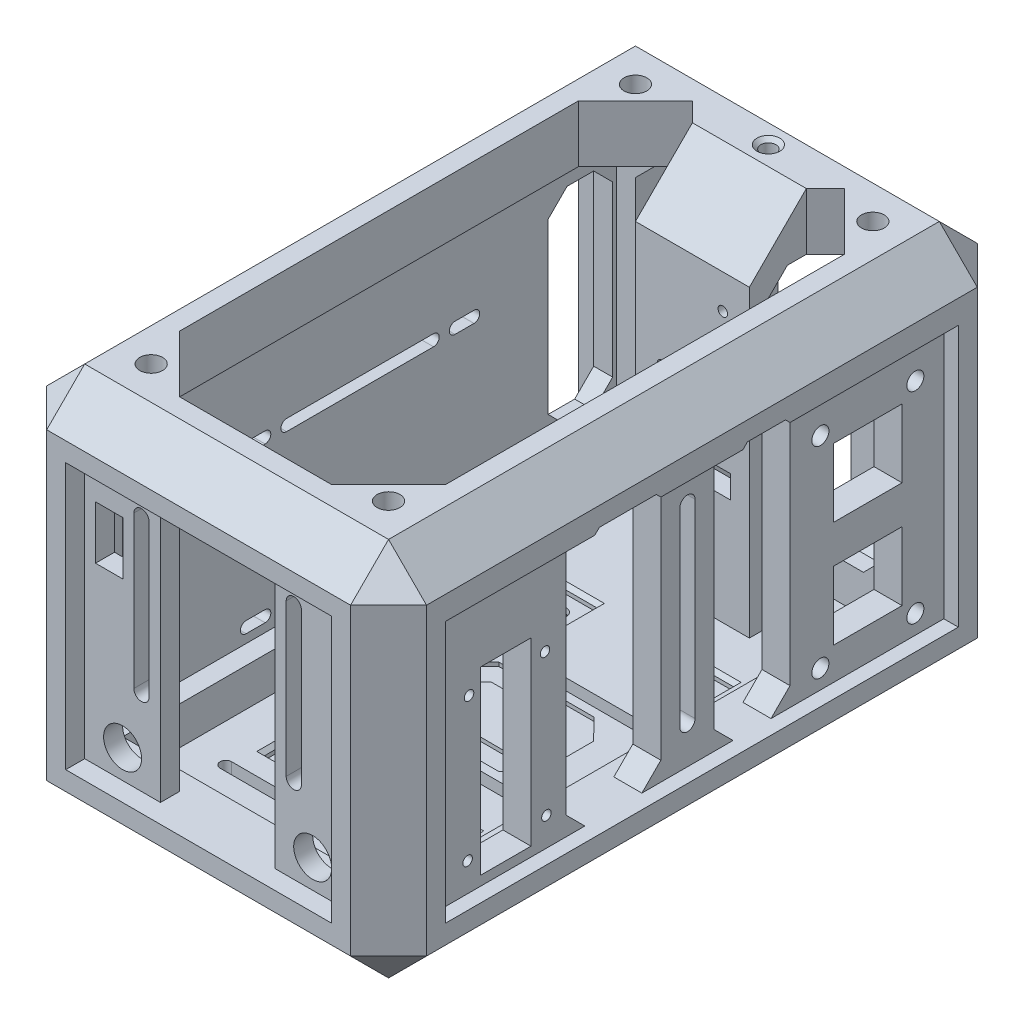
SolidWorks part; units mm, degrees
ref_plane "Front Plane" through (0, 0, 0) normal (0, 0, 1) x (1, 0, 0)
ref_plane "Top Plane" through (0, 0, 0) normal (0, 1, 0) x (1, 0, 0)
ref_plane "Right Plane" through (0, 0, 0) normal (1, 0, 0) x (0, 0, -1)
sketch "Sketch1" plane through (0, 0, 0) normal (0, 0, 1) x (1, 0, 0)
  line L1 (0, 0) -> (100, 0)
  line L2 (0, 0) -> (0, 100)
  line L3 (0, 100) -> (100, 100)
  line L4 (100, 0) -> (100, 100)
  dimension "D1" = 100
  dimension "D2" = 100
extrude "Main Cube" add sketch "Sketch1" against normal blind 165
chamfer "Main Cube Chamfer" distance 10 angle 45 12 edges at (50, 0, -165) (100, 50, -165) (0, 50, -165) (0, 0, -82.5) (0, 50, 0) (50, 0, 0) (100, 0, -82.5) (100, 50, 0) (50, 100, -165) (0, 100, -82.5) (50, 100, 0) (100, 100, -82.5)
sketch "Sketch2" plane through (0, 0, 0) normal (-1, 0, 0) x (0, 0, 1)
  line L1 (-155, 90) -> (-10, 90)
  line L2 (-155, 90) -> (-155, 10)
  line L3 (-155, 10) -> (-10, 10)
  line L4 (-10, 90) -> (-10, 10)
  line L5 (-150, 85) -> (-15, 85)
  line L6 (-150, 85) -> (-150, 15)
  line L7 (-150, 15) -> (-15, 15)
  line L8 (-15, 85) -> (-15, 15)
  dimension "D1" = 5
  dimension "D2" = 5
  dimension "D3" = 5
  dimension "D4" = 5
extrude "Main Cube Hollow Out 1" cut sketch "Sketch2" against normal up to surface (100 mm away) contours L8 L5 L6 L7 region at (0, 50, -82.5) up to face at (100, 50, -82.5)
sketch "Sketch3" plane through (0, 0, -165) normal (0, 0, -1) x (-1, 0, 0)
  line L1 (-90, 90) -> (-10, 90)
  line L2 (-90, 90) -> (-90, 10)
  line L3 (-90, 10) -> (-10, 10)
  line L4 (-10, 90) -> (-10, 10)
  line L5 (-85, 85) -> (-15, 85)
  line L6 (-85, 85) -> (-85, 15)
  line L7 (-85, 15) -> (-15, 15)
  line L8 (-15, 85) -> (-15, 15)
  dimension "D1" = 5
  dimension "D2" = 5
  dimension "D3" = 5
  dimension "D4" = 5
extrude "Main Cube Hollow Out 2" cut sketch "Sketch3" against normal up to surface (165 mm away) contours L8 L5 L6 L7 region at (50, 50, -165) up to face at (50, 50, 0)
sketch "Sketch4" plane through (0, 100, 0) normal (0, 1, 0) x (1, 0, 0)
  line L1 (90, 155) -> (10, 155)
  line L2 (90, 155) -> (90, 10)
  line L3 (90, 10) -> (10, 10)
  line L4 (10, 155) -> (10, 10)
  line L5 (85, 150) -> (15, 150)
  line L6 (85, 150) -> (85, 15)
  line L7 (85, 15) -> (15, 15)
  line L8 (15, 150) -> (15, 15)
  dimension "D1" = 5
  dimension "D2" = 5
  dimension "D3" = 5
  dimension "D4" = 5
extrude "Main Cube Hollow Out 3" cut sketch "Sketch4" against normal up to surface (100 mm away) contours L5 L8 L7 L6 region at (50, 100, -82.5) up to face at (50, 0, -82.5)
sketch "Sketch5" plane through (0, 0, 0) normal (0, -1, 0) x (1, 0, 0)
  line L1 (15, -15) -> (85, -15)
  line L2 (15, -15) -> (15, -150)
  line L3 (15, -150) -> (85, -150)
  line L4 (85, -15) -> (85, -150)
extrude "Bottom" add sketch "Sketch5" against normal blind 5
sketch "Sketch6" plane through (0, 15, 0) normal (0, 1, 0) x (1, 0, 0)
  line L0 (15, 0) -> (15, 15) construction
  line L1 (15, 10) -> (85, 10)
  line L2 (15, 10) -> (15, 5)
  line L3 (15, 5) -> (85, 5)
  line L4 (85, 10) -> (85, 5)
  line L5 (85, 0) -> (85, 15) construction
  line L6 (15, 10) -> (15, 15) construction
  line L7 (15, 5) -> (15, 0) construction
  dimension "D1" = 5
extrude "Camera and Temp Sensor Wall" add sketch "Sketch6" along normal up to surface (70 mm away) up to face at (92.5, 85, -82.5)
sketch "Sketch7" plane through (0, 0, -5) normal (0, 0, 1) x (1, 0, 0)
  line L0 (50, 85) -> (50, 15) construction
  line L1 (85, 85) -> (15, 85) construction
  line L2 (15, 15) -> (85, 15) construction
  line L3 (15, 50) -> (85, 50) construction
  line L4 (15, 85) -> (15, 15) construction
  line L5 (85, 15) -> (85, 85) construction
  line L6 (50, 30) -> (50, 85) construction
  line L8 (34.95, 30) -> (34.95, 85)
  line L9 (34.95, 85) -> (65.05, 85)
  line L10 (65.05, 30) -> (65.05, 85)
  line L11 (15, 22.5) -> (85, 22.5) construction
  line L12 (58.2839, 30) -> (58.2839, 22.5) construction
  line L13 (58.2839, 22.5) -> (58.2839, 15) construction
  line L14 (34.95, 30) -> (24.975, 30) construction
  line L15 (24.975, 30) -> (24.975, 22.5) construction
  line L16 (24.975, 30) -> (15, 30) construction
  line L17 (15, 15) -> (15, 85) construction
  line L18 (65.05, 30) -> (75.025, 30) construction
  line L19 (75.025, 30) -> (75.025, 22.5) construction
  line L20 (75.025, 30) -> (85, 30) construction
  line L21 (85, 85) -> (85, 15) construction
  line L22 (29.95, 77.5) -> (29.95, 37.5) construction
  line L23 (31.95, 77.5) -> (31.95, 37.5)
  line L24 (27.95, 77.5) -> (27.95, 37.5)
  line L25 (70.05, 77.5) -> (70.05, 37.5) construction
  line L26 (72.05, 77.5) -> (72.05, 37.5)
  line L27 (68.05, 77.5) -> (68.05, 37.5)
  line L28 (15, 85) -> (85, 85) construction
  line L29 (15, 15) -> (85, 15) construction
  line L31 (34.95, 30) -> (34.95, 15)
  line L32 (34.95, 15) -> (65.05, 15)
  line L33 (65.05, 30) -> (65.05, 15)
  line L34 (17.85, 69.7469) -> (15, 69.7469) construction
  line L35 (17.85, 75) -> (25.1, 75)
  line L36 (17.85, 75) -> (17.85, 61)
  line L37 (17.85, 61) -> (25.1, 61)
  line L38 (25.1, 75) -> (25.1, 61)
  line L39 (25.1, 69.7469) -> (27.95, 69.7469) construction
  line L40 (34.95, 82.5532) -> (15, 82.5532) construction
  line L41 (65.05, 81.9311) -> (85, 81.9311) construction
  line L42 (31.95, 48.3508) -> (34.95, 48.3508) construction
  line L43 (65.05, 48.3508) -> (68.05, 48.3508) construction
  line L44 (21.475, 75) -> (21.475, 85) construction
  circle A0 centre (24.975, 22.5) radius 5
  circle A1 centre (75.025, 22.5) radius 5
  arc A2 (31.95, 77.5) -> (27.95, 77.5) centre (29.95, 77.5) ccw
  arc A3 (27.95, 37.5) -> (31.95, 37.5) centre (29.95, 37.5) ccw
  arc A4 (72.05, 77.5) -> (68.05, 77.5) centre (70.05, 77.5) ccw
  arc A5 (68.05, 37.5) -> (72.05, 37.5) centre (70.05, 37.5) ccw
  point P36 (29.95, 57.5)
  point P41 (70.05, 57.5)
  dimension "D3" = 10
  dimension "D4" = 10
  dimension "D1" = 30.1
  dimension "D2" = 55
  dimension "D5" = 7.5
  dimension "D6" = 7.25
  dimension "D7" = 7.5
  dimension "D8" = 7.5
  dimension "D9" = 5
  dimension "D10" = 5
  dimension "D11" = 4
  dimension "D12" = 4
  dimension "D13" = 14
  dimension "D14" = 30.1
  dimension "D15" = 10
extrude "Camera and Ext. Temp Sensor Through Holes" cut sketch "Sketch7" against normal up to surface (5 mm away) up to face at (50, 50, -10)
sketch "Sketch8" plane through (0, 15, 0) normal (0, 1, 0) x (1, 0, 0)
  line L0 (15, 150) -> (0, 150) construction
  line L1 (10, 150) -> (5, 150)
  line L2 (10, 150) -> (10, 15)
  line L3 (10, 15) -> (5, 15)
  line L4 (5, 150) -> (5, 15)
  line L5 (15, 15) -> (0, 15) construction
  line L6 (15, 15) -> (10, 15) construction
  line L7 (5, 15) -> (0, 15) construction
  dimension "D1" = 5
extrude "Antenna and Battery Bracket" add sketch "Sketch8" along normal up to surface (70 mm away) up to face at (92.5, 85, -82.5)
chamfer "Top Chamfer 1" distance 5 angle 45 6 edges at (75.025, 85, -10) (24.975, 85, -10) (75.025, 85, -5) (24.975, 85, -5) (65.05, 85, -7.5) (34.95, 85, -7.5)
sketch "Sketch9" plane through (5, 0, 0) normal (-1, 0, 0) x (0, 0, 1)
  line L0 (-136.9322, 71.5) -> (-28.0678, 71.5) construction
  line L1 (-136.9322, 80) -> (-28.0678, 80)
  line L2 (-136.9322, 63) -> (-28.0678, 63)
  line L3 (-82.5, 71.5) -> (-82.5, 85) construction
  line L4 (-150, 85) -> (-15, 85) construction
  line L5 (-112.5, 82.5) -> (-107.5, 82.5) construction
  line L6 (-112.5, 84) -> (-107.5, 84)
  line L7 (-112.5, 81) -> (-107.5, 81)
  line L8 (-52.5, 82.5) -> (-57.5, 82.5) construction
  line L9 (-52.5, 81) -> (-57.5, 81)
  line L10 (-52.5, 84) -> (-57.5, 84)
  line L11 (-52.5, 59.5) -> (-57.5, 59.5) construction
  line L12 (-52.5, 58) -> (-57.5, 58)
  line L13 (-52.5, 61) -> (-57.5, 61)
  line L14 (-107.5, 59.5) -> (-112.5, 59.5) construction
  line L15 (-107.5, 58) -> (-112.5, 58)
  line L16 (-107.5, 61) -> (-112.5, 61)
  line L17 (-110, 84) -> (-110, 85) construction
  line L18 (-15, 85) -> (-150, 85) construction
  line L19 (-110, 81) -> (-110, 80) construction
  line L20 (-110, 61) -> (-110, 63) construction
  line L21 (-55, 61) -> (-55, 63) construction
  line L22 (-55, 81) -> (-55, 80) construction
  line L23 (-55, 84) -> (-55, 85) construction
  line L24 (-110, 84.5) -> (-150, 84.5) construction
  line L25 (-150, 85) -> (-150, 15) construction
  line L26 (-110, 62.5) -> (-150, 62.5) construction
  line L27 (-150, 85) -> (-150, 15) construction
  line L28 (-55, 62.5) -> (-15, 62.5) construction
  line L29 (-55, 84.5) -> (-15, 84.5) construction
  line L30 (-15, 85) -> (-15, 15) construction
  line L31 (-150, 85) -> (-150, 15) construction
  line L32 (-150, 39.25) -> (-15, 39.25) construction
  line L33 (-132.3966, 39.25) -> (-132.3966, 63) construction
  line L34 (-132.3966, 39.25) -> (-132.3966, 15) construction
  line L35 (-150, 15) -> (-15, 15) construction
  line L36 (-101.8419, 59.5) -> (-63.1581, 59.5) construction
  line L37 (-34, 22.5) -> (-131, 22.5)
  line L38 (-34, 22.5) -> (-34, 56)
  line L39 (-34, 56) -> (-131, 56)
  line L40 (-131, 22.5) -> (-131, 56)
  line L41 (-34, 22.5) -> (-131, 56) construction
  line L42 (-34, 56) -> (-131, 22.5) construction
  line L43 (-101.8419, 61) -> (-63.1581, 61)
  line L44 (-101.8419, 58) -> (-63.1581, 58)
  line L45 (-101.8419, 59.5) -> (-107.5, 59.5) construction
  line L46 (-63.1581, 59.5) -> (-57.5, 59.5) construction
  line L47 (-55, 58) -> (-55, 56) construction
  line L48 (-110, 58) -> (-110, 56) construction
  line L49 (-101.8419, 18.75) -> (-63.1581, 18.75) construction
  line L50 (-101.8419, 20.25) -> (-63.1581, 20.25)
  line L51 (-101.8419, 17.25) -> (-63.1581, 17.25)
  line L52 (-57.5, 18.75) -> (-52.5, 18.75) construction
  line L53 (-57.5, 20.25) -> (-52.5, 20.25)
  line L54 (-57.5, 17.25) -> (-52.5, 17.25)
  line L55 (-107.5, 18.75) -> (-112.5, 18.75) construction
  line L56 (-107.5, 17.25) -> (-112.5, 17.25)
  line L57 (-107.5, 20.25) -> (-112.5, 20.25)
  line L58 (-82.5, 18.75) -> (-82.5, 22.5) construction
  line L59 (-82.5, 18.75) -> (-82.5, 15) construction
  line L60 (-63.1581, 82.5) -> (-101.8419, 82.5) construction
  line L61 (-63.1581, 81) -> (-101.8419, 81)
  line L62 (-63.1581, 84) -> (-101.8419, 84)
  line L63 (-150, 47.1044) -> (-149, 47.1044) construction
  line L64 (-149, 77) -> (-132, 77)
  line L65 (-149, 77) -> (-149, 22.5)
  line L66 (-149, 22.5) -> (-132, 22.5)
  line L67 (-132, 77) -> (-132, 22.5)
  line L68 (-33, 22.5) -> (-16, 22.5)
  line L69 (-33, 22.5) -> (-33, 77)
  line L70 (-33, 77) -> (-16, 77)
  line L71 (-16, 22.5) -> (-16, 77)
  line L72 (-132, 47.1044) -> (-131, 47.1044) construction
  line L73 (-34, 47.1044) -> (-33, 47.1044) construction
  line L74 (-16, 47.1044) -> (-15, 47.1044) construction
  line L75 (-146.1678, 77) -> (-146.1678, 84.5) construction
  line L76 (-146.1678, 22.5) -> (-146.1678, 15) construction
  line L77 (-150, 15) -> (-15, 15) construction
  arc A0 (-136.9322, 80) -> (-136.9322, 63) centre (-136.9322, 71.5) ccw
  arc A1 (-28.0678, 63) -> (-28.0678, 80) centre (-28.0678, 71.5) ccw
  arc A2 (-112.5, 84) -> (-112.5, 81) centre (-112.5, 82.5) ccw
  arc A3 (-107.5, 81) -> (-107.5, 84) centre (-107.5, 82.5) ccw
  arc A4 (-52.5, 81) -> (-52.5, 84) centre (-52.5, 82.5) ccw
  arc A5 (-57.5, 84) -> (-57.5, 81) centre (-57.5, 82.5) ccw
  arc A6 (-52.5, 58) -> (-52.5, 61) centre (-52.5, 59.5) ccw
  arc A7 (-57.5, 61) -> (-57.5, 58) centre (-57.5, 59.5) ccw
  arc A8 (-107.5, 58) -> (-107.5, 61) centre (-107.5, 59.5) ccw
  arc A9 (-112.5, 61) -> (-112.5, 58) centre (-112.5, 59.5) ccw
  arc A10 (-101.8419, 61) -> (-101.8419, 58) centre (-101.8419, 59.5) ccw
  arc A11 (-63.1581, 58) -> (-63.1581, 61) centre (-63.1581, 59.5) ccw
  arc A12 (-101.8419, 20.25) -> (-101.8419, 17.25) centre (-101.8419, 18.75) ccw
  arc A13 (-63.1581, 17.25) -> (-63.1581, 20.25) centre (-63.1581, 18.75) ccw
  arc A14 (-57.5, 20.25) -> (-57.5, 17.25) centre (-57.5, 18.75) ccw
  arc A15 (-52.5, 17.25) -> (-52.5, 20.25) centre (-52.5, 18.75) ccw
  arc A16 (-107.5, 17.25) -> (-107.5, 20.25) centre (-107.5, 18.75) ccw
  arc A17 (-112.5, 20.25) -> (-112.5, 17.25) centre (-112.5, 18.75) ccw
  arc A18 (-63.1581, 81) -> (-63.1581, 84) centre (-63.1581, 82.5) ccw
  arc A19 (-101.8419, 84) -> (-101.8419, 81) centre (-101.8419, 82.5) ccw
  point P2 (-82.5, 71.5)
  point P13 (-110, 82.5)
  point P18 (-55, 82.5)
  point P25 (-55, 59.5)
  point P32 (-110, 59.5)
  point P77 (-82.5, 39.25)
  point P87 (-82.5, 59.5)
  point P102 (-82.5, 18.75)
  point P107 (-55, 18.75)
  point P114 (-110, 18.75)
  point P126 (-82.5, 82.5)
  dimension "D2" = 5
  dimension "D3" = 5
  dimension "D4" = 5
  dimension "D5" = 5
  dimension "D6" = 3
  dimension "D7" = 3
  dimension "D8" = 3
  dimension "D9" = 3
  dimension "D10" = 40
  dimension "D11" = 40
  dimension "D12" = 97
  dimension "D13" = 33.5
  dimension "D14" = 1
  dimension "D15" = 2
  dimension "D16" = 17
  dimension "D17" = 3
  dimension "D18" = 5
  dimension "D19" = 5
  dimension "D20" = 1
  dimension "D21" = 1
extrude "Antenna and Battery Zip Tie Holes" cut sketch "Sketch9" against normal up to surface (5 mm away) contours L68 L71 L70 L69 | L67 L64 L65 L66 | L64 A0 L2 L67 | L2 A1 L70 L69 | L6 A3 L7 A2 | L10 A5 L9 A4 | L13 A7 L12 A6 | L43 A11 L44 A10 | L16 A9 L15 A8 | L57 A17 L56 A16 | L50 A13 L51 A12 | L53 A15 L54 A14 | L62 A19 L61 A18 region at (5, 45.1526, -141.0251) region at (5, 70.3505, -138.1472) region at (5, 70.3505, -26.8528) region at (5, 45.1526, -23.9749) up to face at (10, 50, -82.5)
chamfer "Antenna And Battery Wire Pass throughs" distance 5 angle 45 8 edges at (7.5, 22.5, -33) (7.5, 22.5, -16) (7.5, 77, -16) (7.5, 77, -33) (7.5, 77, -149) (7.5, 77, -132) (7.5, 22.5, -132) (7.5, 22.5, -149)
chamfer "Top Chamfer 2" distance 5 angle 45 2 edges at (5, 85, -82.5) (10, 85, -82.5)
sketch "Sketch10" plane through (0, 15, 0) normal (0, 1, 0) x (1, 0, 0)
  line L0 (100, 15) -> (85, 15) construction
  line L1 (88.8093, 15) -> (96.1907, 15)
  line L2 (88.8093, 15) -> (88.8093, 150)
  line L3 (88.8093, 150) -> (96.1907, 150)
  line L4 (96.1907, 15) -> (96.1907, 150)
  line L5 (100, 150) -> (85, 150) construction
  line L6 (88.8093, 15) -> (85, 15) construction
  line L7 (96.1907, 15) -> (100, 15) construction
extrude "SD Card Board and Perf Board Wall" add sketch "Sketch10" along normal up to surface (70 mm away) contours L2 L1 L4 L3 up to face at (92.5, 85, -82.5)
sketch "Sketch11" plane through (96.1907, 0, 0) normal (1, 0, 0) x (0, 0, -1)
  line L0 (25, 60) -> (45, 60) construction
  line L1 (24.625, 22.5) -> (45.375, 22.5) construction
  line L2 (35, 60) -> (35, 22.5) construction
  line L4 (15, 15) -> (150, 15) construction
  line L5 (35, 20) -> (15, 20) construction
  line L6 (15, 85) -> (15, 15) construction
  line L8 (28, 65) -> (41.3059, 65)
  line L9 (28, 65) -> (28, 17.5)
  line L10 (28, 17.5) -> (41.3059, 17.5)
  line L11 (41.3059, 65) -> (41.3059, 17.5)
  line L12 (150, 85) -> (15, 85) construction
  line L14 (25, 60) -> (35, 60) construction
  line L15 (35, 60) -> (45, 60) construction
  line L16 (130, 85) -> (130, 15) construction
  line L17 (117.5, 73) -> (142.5, 73) construction
  line L18 (117.5, 20) -> (142.5, 20) construction
  line L19 (117.5, 20) -> (117.5, 45) construction
  line L20 (139, 51.5) -> (121, 51.5)
  line L21 (139, 51.5) -> (139, 69.5)
  line L22 (139, 69.5) -> (121, 69.5)
  line L23 (121, 51.5) -> (121, 69.5)
  line L24 (139, 51.5) -> (121, 69.5) construction
  line L25 (139, 69.5) -> (121, 51.5) construction
  line L26 (139, 23.5) -> (121, 23.5)
  line L27 (139, 23.5) -> (139, 41.5)
  line L28 (139, 41.5) -> (121, 41.5)
  line L29 (121, 23.5) -> (121, 41.5)
  line L30 (139, 23.5) -> (121, 41.5) construction
  line L31 (139, 41.5) -> (121, 23.5) construction
  line L32 (117.5, 45) -> (142.5, 45) construction
  line L33 (142.5, 45) -> (142.5, 20) construction
  line L34 (121, 39.018) -> (117.5, 39.018) construction
  line L35 (124.5972, 41.5) -> (124.5972, 45) construction
  line L36 (139, 39.018) -> (142.5, 39.018) construction
  line L37 (124.5972, 23.5) -> (124.5972, 20) construction
  line L38 (117.5, 73) -> (117.5, 48) construction
  line L39 (117.5, 48) -> (142.5, 48) construction
  line L40 (142.5, 48) -> (142.5, 73) construction
  line L41 (124.5972, 51.5) -> (124.5972, 48) construction
  line L42 (124.5972, 69.5) -> (124.5972, 73) construction
  line L43 (117.5, 71.1246) -> (121, 71.1246) construction
  line L44 (139, 71.1246) -> (142.5, 71.1246) construction
  line L45 (150, 85) -> (150, 15) construction
  line L46 (82.5, 85) -> (82.5, 15) construction
  line L47 (150, 15) -> (15, 15) construction
  line L48 (82.5, 75) -> (82.5, 25) construction
  line L49 (84.5, 75) -> (84.5, 25)
  line L50 (80.5, 75) -> (80.5, 25)
  line L51 (150, 85) -> (15, 85) construction
  line L52 (75.5, 15) -> (50.5, 15)
  line L53 (75.5, 15) -> (75.5, 85)
  line L54 (75.5, 85) -> (50.5, 85)
  line L55 (50.5, 15) -> (50.5, 85)
  line L57 (89.5, 85) -> (109.5, 85)
  line L58 (89.5, 85) -> (89.5, 15)
  line L59 (89.5, 15) -> (109.5, 15)
  line L60 (109.5, 85) -> (109.5, 15)
  circle A0 centre (25, 60) radius 1.25
  circle A1 centre (24.625, 22.5) radius 1.25
  circle A2 centre (45.375, 22.5) radius 1.25
  circle A3 centre (45, 60) radius 1.25
  circle A4 centre (117.5, 73) radius 2.25
  circle A5 centre (142.5, 73) radius 2.25
  circle A6 centre (142.5, 20) radius 2.25
  circle A7 centre (117.5, 20) radius 2.25
  arc A8 (84.5, 75) -> (80.5, 75) centre (82.5, 75) ccw
  arc A9 (80.5, 25) -> (84.5, 25) centre (82.5, 25) ccw
  point P37 (130, 20)
  point P38 (130, 50)
  point P39 (130, 60.5)
  point P44 (130, 32.5)
  point P49 (130, 73)
  point P78 (82.5, 50)
  dimension "D3" = 2.5
  dimension "D4" = 2.5
  dimension "D5" = 2.5
  dimension "D6" = 2.5
  dimension "D12" = 4.5
  dimension "D13" = 4.5
  dimension "D14" = 4.5
  dimension "D15" = 4.5
  dimension "D1" = 20.75
  dimension "D2" = 20
  dimension "D7" = 37.5
  dimension "D8" = 5
  dimension "D9" = 20
  dimension "D10" = 5
  dimension "D11" = 3
  dimension "D16" = 25
  dimension "D17" = 25
  dimension "D18" = 18
  dimension "D19" = 18
  dimension "D20" = 5
  dimension "D21" = 25
  dimension "D22" = 25
  dimension "D23" = 10
  dimension "D24" = 7.5
  dimension "D25" = 10
  dimension "D26" = 10
  dimension "D27" = 4
  dimension "D28" = 5
  dimension "D29" = 5
  dimension "D30" = 25
  dimension "D31" = 20
  dimension "D32" = 7.5
extrude "SD Card Board and Perf Board Through Holes" cut sketch "Sketch11" against normal up to surface (7.3814 mm away) up to face at (88.8093, 50, -82.5)
chamfer "Top Chamfer 3" distance 5 angle 45 14 edges at (92.5, 15, -75.5) (92.5, 15, -50.5) (96.1907, 85, -129.75) (92.5, 85, -109.5) (92.5, 85, -89.5) (96.1907, 85, -82.5) (92.5, 85, -75.5) (92.5, 85, -50.5) (96.1907, 85, -32.75) (88.8093, 85, -129.75) (88.8093, 85, -82.5) (88.8093, 85, -32.75) (92.5, 15, -89.5) (92.5, 15, -109.5)
sketch "Sketch13" plane through (0, 5, 0) normal (0, 1, 0) x (1, 0, 0)
  line L0 (15, 150) -> (85, 150) construction
  line L1 (35, 150) -> (65, 150)
  line L2 (35, 150) -> (35, 130)
  line L3 (35, 130) -> (65, 130)
  line L4 (65, 150) -> (65, 130)
  line L5 (15, 150) -> (35, 150) construction
  line L6 (65, 150) -> (85, 150) construction
  dimension "D1" = 30
  dimension "D2" = 20
extrude "Pressure Sensor Bracket 1" add sketch "Sketch13" along normal up to surface (10 mm away) up to face at (50, 15, -7.5)
sketch "Sketch14" plane through (0, 15, 0) normal (0, 1, 0) x (1, 0, 0)
  line L0 (65, 130) -> (65, 150) construction
  line L1 (35, 130) -> (65, 130)
  line L2 (35, 130) -> (35, 135)
  line L3 (35, 135) -> (65, 135)
  line L4 (65, 130) -> (65, 135)
  dimension "D1" = 5
extrude "Pressure Sensor Bracket 2" add sketch "Sketch14" along normal up to surface (85 mm away) up to face at (50, 100, -82.5)
sketch "Sketch16" plane through (0, 100, 0) normal (0, 1, 0) x (1, 0, 0)
  line L1 (35, 135) -> (65, 135)
  line L2 (35, 135) -> (35, 150)
  line L3 (35, 150) -> (65, 150)
  line L4 (65, 135) -> (65, 150)
extrude "Pressure Sensor Bracket 3" add sketch "Sketch16" against normal up to surface (15 mm away) up to face at (92.5, 85, -99.5)
sketch "Sketch17" plane through (0, 15, 0) normal (0, 1, 0) x (1, 0, 0)
  line L0 (65, 135) -> (35, 135) construction
  line L1 (65, 150) -> (60, 150)
  line L2 (65, 150) -> (65, 135)
  line L3 (65, 135) -> (60, 135)
  line L4 (60, 150) -> (60, 135)
  line L6 (35, 150) -> (40, 150)
  line L7 (35, 150) -> (35, 135)
  line L8 (35, 135) -> (40, 135)
  line L9 (40, 150) -> (40, 135)
  dimension "D1" = 5
  dimension "D2" = 5
extrude "Pressure Sensor Bracket 4" add sketch "Sketch17" along normal blind 20
chamfer "Top Chamfer 4" distance 5 angle 45 1 edges at (50, 85, -135)
chamfer "Pressure Sensor Bracket Chamfer" distance 5 angle 45 4 edges at (37.5, 35, -150) (62.5, 35, -150) (37.5, 35, -135) (62.5, 35, -135)
chamfer "Top Chamfer 5" distance 10 angle 45 2 edges at (85, 85, -157.5) (15, 85, -157.5)
chamfer "Bottom Chamfer 1" distance 10 angle 45 2 edges at (15, 15, -157.5) (85, 15, -157.5)
sketch "Sketch18" plane through (35, 0, 0) normal (-1, 0, 0) x (0, 0, 1)
  line L0 (-150, 22.5) -> (-130, 22.5) construction
  line L1 (-150, 30) -> (-150, 15) construction
  line L2 (-130, 100) -> (-130, 5) construction
  circle A0 centre (-140, 22.5) radius 5
  dimension "D1" = 10
extrude "Wire Management Hole" cut sketch "Sketch18" against normal up to surface (30 mm away) up to face at (65, 51.25, -142.0833)
sketch "Sketch19" plane through (0, 0, -135) normal (0, 0, -1) x (-1, 0, 0)
  line L0 (-60, 40) -> (-40, 40) construction
  line L1 (-50, 40) -> (-50, 48) construction
  line L2 (-50, 48) -> (-56.35, 48) construction
  line L3 (-50, 48) -> (-43.65, 48) construction
  line L4 (-60, 40) -> (-60, 22.5) construction
  line L5 (-60, 34) -> (-40, 34)
  line L6 (-60, 34) -> (-60, 40)
  line L7 (-60, 40) -> (-40, 40)
  line L8 (-40, 34) -> (-40, 40)
  line L10 (-40, 40) -> (-35, 40) construction
  circle A0 centre (-56.35, 48) radius 1.25
  circle A1 centre (-43.65, 48) radius 1.25
  dimension "D1" = 2.5
  dimension "D2" = 2.5
  dimension "D3" = 12.7
  dimension "D4" = 6
  dimension "D5" = 8
extrude "Pressure Sensor Through Hole" cut sketch "Sketch19" against normal up to surface (5 mm away) up to face at (50, 52.5, -130)
sketch "Sketch20" plane through (0, 15, 0) normal (0, 1, 0) x (1, 0, 0)
  line L0 (75, 165) -> (25, 165) construction
  line L1 (70, 165) -> (62.5, 165)
  line L2 (70, 165) -> (70, 159.3045)
  line L3 (70, 159.3045) -> (62.5, 159.3045)
  line L4 (62.5, 165) -> (62.5, 159.3045)
  line L5 (75, 165) -> (70, 165) construction
  line L6 (30, 165) -> (37.5, 165)
  line L7 (30, 165) -> (30, 159.3045)
  line L8 (30, 159.3045) -> (37.5, 159.3045)
  line L9 (37.5, 165) -> (37.5, 159.3045)
  line L10 (30, 165) -> (25, 165) construction
  dimension "D1" = 5
  dimension "D2" = 7.5
extrude "Boss-Extrude13" add sketch "Sketch20" along normal up to surface (70 mm away) up to face at (92.5, 85, -99.5)
sketch "Sketch21" plane through (0, 0, -165) normal (0, 0, -1) x (-1, 0, 0)
  line L0 (-15, 25) -> (-30, 25)
  line L1 (-30, 85) -> (-30, 15) construction
  line L2 (-30, 25) -> (-30, 15)
  line L3 (-30, 15) -> (-25, 15)
  line L4 (-25, 15) -> (-15, 25)
  line L5 (-85, 25) -> (-70, 25)
  line L6 (-70, 85) -> (-70, 15) construction
  line L7 (-70, 25) -> (-70, 15)
  line L8 (-70, 15) -> (-75.025, 15)
  line L9 (-85, 15) -> (-65.05, 15) construction
  line L10 (-75.025, 15) -> (-85, 25)
extrude "Boss-Extrude14" add sketch "Sketch21" against normal up to surface (5.6955 mm away) up to face at (66.25, 50, -159.3045)
chamfer "Chamfer10" distance 5 angle 45 2 edges at (31.25, 15, -159.3045) (68.75, 15, -159.3045)
chamfer "Chamfer11" distance 5 angle 45 2 edges at (37.5, 15, -159.6523) (62.5, 15, -159.6523)
chamfer "Chamfer12" distance 5 angle 45 2 edges at (37.5, 85, -162.1523) (62.5, 85, -162.1523)
chamfer "Chamfer14" distance 15 angle 45 1 edges at (50, 100, -130)
sketch "Sketch23" plane through (0, 15, 0) normal (0, 1, 0) x (1, 0, 0)
  line L0 (50, 135) -> (50, 165) construction
  line L1 (60, 135) -> (40, 135) construction
  line L2 (57.5, 165) -> (42.5, 165) construction
  line L3 (60, 150) -> (40, 150) construction
  circle A0 centre (50, 150) radius 2
  dimension "D1" = 4
extrude "Cut-Extrude9" cut sketch "Sketch23" against normal up to surface and the other way up to surface up to face at (50, 0, -82.5) other way up to face at (50, 100, -115)
chamfer "Chamfer15" distance 1 angle 45 3 edges at (50, 0, -152) (50, 15, -152) (50, 100, -148)
sketch "Sketch24" plane through (0, 5, 0) normal (0, 1, 0) x (1, 0, 0)
  line L0 (50, 130) -> (50, 15) construction
  line L1 (35, 130) -> (65, 130) construction
  line L2 (85, 15) -> (15, 15) construction
  line L3 (72.5, 117.3146) -> (27.5, 117.3146) construction
  line L4 (72.5, 117.3146) -> (72.5, 40.8146) construction
  line L5 (72.5, 40.8146) -> (27.5, 40.8146) construction
  line L6 (27.5, 40.8146) -> (27.5, 117.3146) construction
  line L7 (63, 117.3146) -> (63, 117.8146)
  line L8 (72.5, 117.3146) -> (63, 117.3146)
  line L9 (72.5, 117.3146) -> (72.5, 107.8146)
  line L10 (72.5, 107.8146) -> (63, 107.8146)
  line L11 (63, 117.3146) -> (63, 107.8146)
  line L12 (27.5, 117.3146) -> (37, 117.3146)
  line L13 (27.5, 117.3146) -> (27.5, 107.8146)
  line L14 (27.5, 107.8146) -> (37, 107.8146)
  line L15 (37, 117.3146) -> (37, 107.8146)
  line L16 (27.5, 40.8146) -> (37, 40.8146)
  line L17 (27.5, 40.8146) -> (27.5, 50.3146)
  line L18 (27.5, 50.3146) -> (37, 50.3146)
  line L19 (37, 40.8146) -> (37, 50.3146)
  line L20 (72.5, 40.8146) -> (63, 40.8146)
  line L21 (72.5, 40.8146) -> (72.5, 50.0646)
  line L22 (72.5, 50.0646) -> (63, 50.0646)
  line L23 (63, 40.8146) -> (63, 50.0646)
  line L24 (63, 117.8146) -> (73, 117.8146)
  line L25 (73, 117.8146) -> (73, 107.8146)
  line L26 (73, 107.8146) -> (72.5, 107.8146)
  line L27 (72.5, 50.0646) -> (73, 50.0646)
  line L28 (73, 50.0646) -> (73, 40.3146)
  line L29 (73, 40.3146) -> (63, 40.3146)
  line L30 (63, 40.3146) -> (63, 40.8146)
  line L31 (37, 40.8146) -> (37, 40.3146)
  line L32 (37, 40.3146) -> (27, 40.3146)
  line L33 (27, 40.3146) -> (27, 50.3146)
  line L34 (27, 50.3146) -> (27.5, 50.3146)
  line L35 (37, 117.3146) -> (37, 117.8146)
  line L36 (37, 117.8146) -> (27, 117.8146)
  line L37 (27, 117.8146) -> (27, 107.8146)
  line L38 (27, 107.8146) -> (27.5, 107.8146)
  point P6 (50, 117.3146)
  dimension "D1" = 76.5
  dimension "D2" = 45
  dimension "D3" = 9.5
  dimension "D4" = 9.5
  dimension "D5" = 9.5
  dimension "D6" = 9.5
  dimension "D7" = 9.5
  dimension "D8" = 9.5
  dimension "D9" = 9.25
  dimension "D10" = 9.5
  dimension "D11" = 0.5
  dimension "D12" = 0.5
  dimension "D13" = 0.5
  dimension "D14" = 0.5
  dimension "D15" = 0.5
  dimension "D16" = 0.5
  dimension "D17" = 0.5
  dimension "D18" = 0.5
extrude "Cut-Extrude10" cut sketch "Sketch24" against normal blind 2 contours L26 L25 L24 L7 L8 L9 | L8 L11 L10 L9 | L37 L38 L13 L12 L35 L36 | L15 L12 L13 L14 | L34 L33 L32 L31 L16 L17 | L16 L19 L18 L17 | L23 L20 L21 L22 | L30 L29 L28 L27 L21 L20 region at (63.1414, 5, -117.5646) region at (67.75, 5, -112.5646) region at (27.3586, 5, -112.5646) region at (32.25, 5, -112.5646) region at (32.25, 5, -45.5646) region at (32.25, 5, -40.6732) region at (72.6397, 5, -45.4396) region at (67.75, 5, -45.4396)
chamfer "Chamfer16" distance 1 angle 45 16 edges at (68, 5, -40.3146) (73, 5, -45.1896) (68, 5, -50.0646) (63, 5, -45.1896) (27, 5, -45.3146) (32, 5, -40.3146) (37, 5, -45.3146) (32, 5, -50.3146) (27, 5, -112.8146) (32, 5, -107.8146) (32, 5, -117.8146) (37, 5, -112.8146) (63, 5, -112.8146) (68, 5, -107.8146) (73, 5, -112.8146) (68, 5, -117.8146)
sketch "Sketch25" plane through (0, 3, 0) normal (0, 1, 0) x (1, 0, 0)
  line L0 (73, 117.8146) -> (63, 107.8146) construction
  line L1 (63, 117.8146) -> (73, 107.8146) construction
  circle A0 centre (68, 112.8146) radius 2
  dimension "D1" = 4
extrude "Cut-Extrude11" cut sketch "Sketch25" against normal up to surface (3 mm away) up to face at (50, 0, -153)
sketch "Sketch26" plane through (0, 3, 0) normal (0, 1, 0) x (1, 0, 0)
  line L0 (37, 117.8146) -> (27, 107.8146) construction
  line L1 (27, 117.8146) -> (27, 107.8146) construction
  line L2 (27, 117.8146) -> (27, 107.8146) construction
  line L3 (27, 107.8146) -> (27, 117.8146) construction
  line L4 (27, 117.8146) -> (37, 107.8146) construction
  circle A0 centre (32, 112.8146) radius 2
  dimension "D1" = 4
sketch "Sketch27" plane through (0, 3, 0) normal (0, 1, 0) x (1, 0, 0)
  line L0 (37, 50.3146) -> (27, 40.3146) construction
  line L1 (27, 40.3146) -> (27, 50.3146) construction
  line L2 (27, 50.3146) -> (37, 40.3146) construction
  line L3 (73, 50.0646) -> (63, 40.3146) construction
  line L4 (63, 40.3146) -> (63, 50.0646) construction
  line L5 (63, 50.0646) -> (73, 40.3146) construction
  circle A0 centre (32, 45.3146) radius 2
  circle A1 centre (68, 45.1896) radius 2
  dimension "D1" = 4
  dimension "D2" = 4
extrude "Cut-Extrude12" cut sketch "Sketch27" against normal up to surface (3 mm away) up to face at (68, 0, -114.8146)
extrude "Cut-Extrude13" cut sketch "Sketch26" against normal up to surface (3 mm away) up to face at (32, 0, -47.3146)
chamfer "Chamfer17" distance 1.5 angle 45 4 edges at (68, 0, -114.8146) (68, 0, -47.1896) (32, 0, -47.3146) (32, 0, -114.8146)
chamfer "Chamfer18" distance 5 angle 45 2 edges at (63.75, 85, -159.3045) (36.25, 85, -159.3045)
chamfer "Chamfer19" distance 5 angle 45 2 edges at (65, 92.5, -150) (35, 92.5, -150)
sketch "Sketch28" plane through (0, 0, -135) normal (0, 0, -1) x (-1, 0, 0)
  line L0 (-50, 80) -> (-50, 40) construction
  line L1 (-35, 80) -> (-65, 80) construction
  line L2 (-40, 40) -> (-60, 40) construction
  line L3 (-47, 55.68) -> (-60, 55.68) construction
  line L4 (-42, 55.68) -> (-58, 55.68)
  line L5 (-42, 55.68) -> (-42, 76)
  line L6 (-42, 76) -> (-58, 76)
  line L7 (-58, 55.68) -> (-58, 76)
  line L8 (-42, 55.68) -> (-58, 76) construction
  line L9 (-42, 76) -> (-58, 55.68) construction
  line L10 (-47, 53.18) -> (-60, 53.18)
  line L11 (-47, 58.18) -> (-60, 58.18)
  circle A0 centre (-58, 76) radius 1.25
  circle A1 centre (-42, 55.68) radius 1.25
  arc A2 (-47, 53.18) -> (-47, 58.18) centre (-47, 55.68) ccw
  arc A3 (-60, 58.18) -> (-60, 53.18) centre (-60, 55.68) ccw
  point P6 (-50, 65.84)
  point P15 (-53.5, 55.68)
  point P20 (-47.2061, 55.0685)
  dimension "D3" = 2.5
  dimension "D4" = 2.5
  dimension "D1" = 20.32
  dimension "D2" = 16
  dimension "D5" = 5
  dimension "D6" = 5
  dimension "D7" = 2
  dimension "D8" = 4
extrude "Cut-Extrude14" cut sketch "Sketch28" against normal up to surface (5 mm away) contours L6 A0 L7 | L7 A0 L6 | L11 A3 L10 A2 L4 L7 | L4 A2 L11 L7 | L4 A1 L5 | L5 A1 L4 region at (41.8232, 55.5032, -135) region at (42.5305, 56.2105, -135) region at (54.7372, 54.9221, -135) region at (51.5062, 56.9014, -135) region at (57.4695, 75.4695, -135) region at (58.1768, 76.1768, -135) up to face at (50, 37, -130)
sketch "Sketch29" plane through (0, 100, 0) normal (0, 1, 0) x (1, 0, 0)
  line L0 (15, 30) -> (30, 15)
  line L1 (15, 15) -> (15, 150) construction
  line L2 (85, 15) -> (15, 15) construction
  line L3 (30, 15) -> (15, 15)
  line L4 (15, 15) -> (15, 30)
  line L5 (85, 30) -> (70, 15)
  line L6 (85, 150) -> (85, 15) construction
  line L7 (70, 15) -> (85, 15)
  line L8 (85, 15) -> (85, 30)
  line L9 (85, 135) -> (70, 150)
  line L10 (65, 150) -> (85, 150) construction
  line L11 (70, 150) -> (85, 150)
  line L12 (85, 150) -> (85, 135)
  line L13 (15, 135) -> (30, 150)
  line L14 (15, 150) -> (15, 15) construction
  line L15 (15, 150) -> (35, 150) construction
  line L16 (30, 150) -> (15, 150)
  line L17 (15, 150) -> (15, 135)
  line L18 (15, 15) -> (22.5, 22.5) construction
  line L19 (85, 15) -> (77.5, 22.5) construction
  line L20 (77.5, 142.5) -> (85, 150) construction
  line L21 (15, 150) -> (22.5, 142.5) construction
  circle A2 centre (18.75, 18.75) radius 3
  circle A3 centre (18.75, 146.25) radius 3
  circle A4 centre (81.25, 146.25) radius 3
  circle A5 centre (81.25, 18.75) radius 3
  dimension "D9" = 6
  dimension "D10" = 6
  dimension "D11" = 6
  dimension "D12" = 6
  dimension "D1" = 15
  dimension "D2" = 15
  dimension "D3" = 15
  dimension "D4" = 15
  dimension "D5" = 15
  dimension "D6" = 15
  dimension "D7" = 15
  dimension "D8" = 15
extrude "Boss-Extrude16" add sketch "Sketch29" against normal up to surface (15 mm away) up to face at (50, 85, -7.5)
sketch "Sketch31" plane through (0, 5, 0) normal (0, 1, 0) x (1, 0, 0)
  line L0 (25, 22.1573) -> (75, 22.1573) construction
  line L1 (25, 23.6573) -> (75, 23.6573)
  line L2 (25, 20.6573) -> (75, 20.6573)
  line L3 (25, 32.1573) -> (75, 32.1573) construction
  line L4 (25, 33.6573) -> (75, 33.6573)
  line L5 (25, 30.6573) -> (75, 30.6573)
  line L6 (30.7645, 15) -> (30.7645, 20.6573) construction
  line L7 (85, 15) -> (15, 15) construction
  line L8 (30.7645, 23.6573) -> (30.7645, 30.6573) construction
  line L9 (30.7645, 33.6573) -> (30.7645, 39.3146) construction
  line L10 (38, 39.3146) -> (26, 39.3146) construction
  line L11 (25, 22.1573) -> (15, 22.1573) construction
  line L12 (15, 15) -> (15, 150) construction
  line L13 (75, 22.1573) -> (85, 22.1573) construction
  line L14 (85, 150) -> (85, 15) construction
  line L15 (25, 32.1573) -> (25, 119.077) construction
  line L16 (75, 32.1573) -> (75, 119.077) construction
  line L17 (25, 22.1573) -> (25, 32.1573) construction
  line L18 (75, 22.1573) -> (75, 32.1573) construction
  line L19 (25, 62.8146) -> (75, 62.8146) construction
  line L20 (25, 64.3146) -> (75, 64.3146)
  line L21 (25, 61.3146) -> (75, 61.3146)
  line L22 (25, 95.3146) -> (75, 95.3146) construction
  line L23 (25, 96.8146) -> (75, 96.8146)
  line L24 (25, 93.8146) -> (75, 93.8146)
  line L25 (30.7645, 51.3146) -> (30.7645, 61.3146) construction
  line L26 (26, 51.3146) -> (38, 51.3146) construction
  line L27 (30.7645, 96.8146) -> (30.7645, 106.8146) construction
  line L28 (38, 106.8146) -> (26, 106.8146) construction
  line L29 (32.8156, 64.3146) -> (32.8156, 93.8146) construction
  arc A0 (25, 23.6573) -> (25, 20.6573) centre (25, 22.1573) ccw
  arc A1 (75, 20.6573) -> (75, 23.6573) centre (75, 22.1573) ccw
  arc A2 (25, 33.6573) -> (25, 30.6573) centre (25, 32.1573) ccw
  arc A3 (75, 30.6573) -> (75, 33.6573) centre (75, 32.1573) ccw
  arc A4 (25, 64.3146) -> (25, 61.3146) centre (25, 62.8146) ccw
  arc A5 (75, 61.3146) -> (75, 64.3146) centre (75, 62.8146) ccw
  arc A6 (25, 96.8146) -> (25, 93.8146) centre (25, 95.3146) ccw
  arc A7 (75, 93.8146) -> (75, 96.8146) centre (75, 95.3146) ccw
  point P2 (50, 22.1573)
  point P9 (50, 32.1573)
  point P38 (50, 62.8146)
  point P45 (50, 95.3146)
  dimension "D1" = 3
  dimension "D2" = 3
  dimension "D3" = 7
  dimension "D4" = 10
  dimension "D5" = 3
  dimension "D6" = 3
  dimension "D7" = 10
extrude "Cut-Extrude15" cut sketch "Sketch31" against normal up to surface (5 mm away) up to face at (68, 0, -116.3146)
sketch "Sketch32" plane through (0, 5, 0) normal (0, 1, 0) x (1, 0, 0)
  line L0 (32, 45.3146) -> (32, 112.8146) construction
  line L1 (32, 112.8146) -> (68, 112.8146) construction
  line L2 (68, 112.8146) -> (68, 45.1896) construction
  line L3 (68, 45.1896) -> (32, 45.3146) construction
  line L4 (32, 79.0646) -> (32, 86.0021)
  line L5 (32, 86.0021) -> (37.5314, 91.5335)
  line L6 (37.5314, 91.5335) -> (62.5314, 91.5335)
  line L7 (62.5314, 91.5335) -> (68, 86.0021)
  line L8 (68, 86.0021) -> (68, 79.0021)
  line L9 (68, 79.0021) -> (68, 72.0021)
  line L10 (68, 72.0021) -> (62.5314, 66.5957)
  line L11 (62.5314, 66.5957) -> (37.5314, 66.5957)
  line L12 (37.5314, 66.5957) -> (32, 72.1271)
  line L13 (32, 72.1271) -> (32, 79.0646)
  line L14 (37.5314, 66.5957) -> (37.5314, 91.5335) construction
  line L15 (62.5314, 66.5957) -> (62.5314, 91.5335) construction
  line L16 (32, 72.1271) -> (68, 72.0021) construction
  line L17 (32, 86.0021) -> (68, 86.0021) construction
  line L18 (32, 66.5957) -> (32, 72.1271) construction
  line L19 (32, 86.0021) -> (32, 91.5335) construction
  line L20 (40.9845, 72.0959) -> (37.5314, 75.549)
  line L21 (37.5314, 75.549) -> (37.5314, 82.549)
  line L22 (37.5314, 82.549) -> (40.9845, 86.0021)
  line L23 (40.9845, 86.0021) -> (59.0981, 86.0021)
  line L24 (59.0981, 86.0021) -> (62.5314, 82.5293)
  line L25 (62.5314, 82.5293) -> (62.5314, 75.4665)
  line L26 (62.5314, 75.4665) -> (59.0587, 72.0331)
  line L27 (59.0587, 72.0331) -> (40.9845, 72.0959)
  dimension "D1" = 25
  dimension "D2" = 7
  dimension "D3" = 7
extrude "Cut-Extrude16" cut sketch "Sketch32" against normal blind 1
